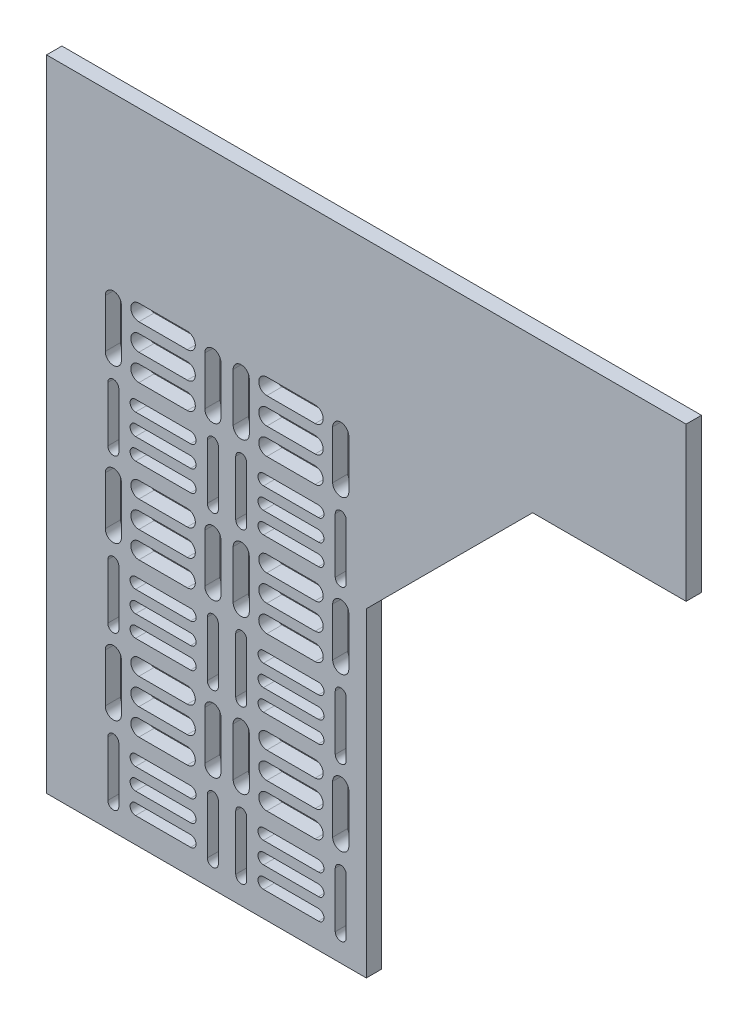
SolidWorks part; units mm, degrees
ref_plane "XY" through (0, 0, 0) normal (0, 0, 1) x (1, 0, 0)
ref_plane "-XZ" through (0, 0, 0) normal (0, 1, 0) x (1, 0, 0)
ref_plane "ZY" through (0, 0, 0) normal (1, 0, 0) x (0, 0, -1)
sketch "Esquisse1" plane through (0, 0, 0) normal (0, 0, 1) x (1, 0, 0)
  line L0 (0, 0) -> (0, 125)
  line L13 (0, 125) -> (125, 125)
  line L19 (125, 125) -> (125, 95)
  line L20 (125, 95) -> (95, 95)
  line L21 (62.5, 62.5) -> (62.5, 0)
  line L22 (62.5, 0) -> (0, 0)
  line L23 (95, 95) -> (62.5, 62.5)
  dimension "D1" = 30
  dimension "D4" = 125
  dimension "D2" = 30
  dimension "D3" = 125
  dimension "D5" = 62.5
  dimension "D6" = 62.5
extrude "Boss.-Extru.1" add sketch "Esquisse1" along normal blind 3 contours L13 L19 L20 L23 L21 L22 L0
sketch "Esquisse2" plane through (0, 0, 3) normal (0, 0, 1) x (1, 0, 0)
  line L0 (43.05, 83.7) -> (52.5, 83.7)
  line L3 (43.05, 90.425) -> (52.5, 90.425) construction
  line L4 (43.05, 92) -> (52.5, 92)
  line L5 (43.05, 88.85) -> (52.5, 88.85)
  line L6 (57.5, 90) -> (57.5, 80.55) construction
  line L7 (59.075, 90) -> (59.075, 80.55)
  line L8 (55.925, 90) -> (55.925, 80.55)
  line L9 (0, 125) -> (125, 125) construction
  line L10 (62.5, 62.5) -> (62.5, 0) construction
  line L11 (43.05, 86.85) -> (52.5, 86.85)
  line L12 (43.05, 78.55) -> (52.5, 78.55)
  line L13 (43.05, 81.7) -> (52.5, 81.7)
  line L18 (42.4, 74.325) -> (53.15, 74.325) construction
  line L28 (47.775, 92) -> (47.775, 88.85) construction
  line L29 (42.4, 75.4) -> (53.15, 75.4)
  line L30 (36.475, 90) -> (36.475, 80.55)
  line L31 (39.625, 90) -> (39.625, 80.55)
  line L32 (42.4, 73.25) -> (53.15, 73.25)
  line L34 (57.5, 64.8) -> (57.5, 75.55) construction
  line L35 (56.425, 75.55) -> (56.425, 64.8)
  line L36 (58.575, 75.55) -> (58.575, 64.8)
  line L37 (47.775, 73.25) -> (47.775, 75.4) construction
  line L38 (42.4, 69.1) -> (53.15, 69.1)
  line L39 (42.4, 71.25) -> (53.15, 71.25)
  line L40 (42.4, 64.95) -> (53.15, 64.95)
  line L41 (42.4, 67.1) -> (53.15, 67.1)
  line L42 (39.125, 75.55) -> (39.125, 64.8)
  line L43 (36.975, 75.55) -> (36.975, 64.8)
  circle A5 centre (43.05, 90.425) radius 1.575 construction
  circle A6 centre (46.2, 90.425) radius 1.575 construction
  circle A7 centre (49.35, 90.425) radius 1.575 construction
  circle A8 centre (52.5, 90.425) radius 1.575 construction
  arc A9 (43.05, 92) -> (43.05, 88.85) centre (43.05, 90.425) ccw
  arc A10 (52.5, 92) -> (52.5, 88.85) centre (52.5, 90.425) cw
  circle A11 centre (57.5, 90) radius 1.575 construction
  circle A12 centre (57.5, 86.85) radius 1.575 construction
  circle A13 centre (57.5, 83.7) radius 1.575 construction
  circle A14 centre (57.5, 80.55) radius 1.575 construction
  arc A15 (59.075, 90) -> (55.925, 90) centre (57.5, 90) ccw
  arc A16 (59.075, 80.55) -> (55.925, 80.55) centre (57.5, 80.55) cw
  arc A17 (52.5, 86.85) -> (52.5, 83.7) centre (52.5, 85.275) cw
  arc A18 (43.05, 86.85) -> (43.05, 83.7) centre (43.05, 85.275) ccw
  arc A19 (52.5, 81.7) -> (52.5, 78.55) centre (52.5, 80.125) cw
  arc A20 (43.05, 81.7) -> (43.05, 78.55) centre (43.05, 80.125) ccw
  arc A41 (36.475, 90) -> (39.625, 90) centre (38.05, 90) cw
  arc A42 (36.475, 80.55) -> (39.625, 80.55) centre (38.05, 80.55) ccw
  circle A45 centre (42.4, 74.325) radius 1.075 construction
  circle A46 centre (44.55, 74.325) radius 1.075 construction
  circle A47 centre (46.7, 74.325) radius 1.075 construction
  circle A48 centre (51, 74.325) radius 1.075 construction
  circle A49 centre (53.15, 74.325) radius 1.075 construction
  circle A50 centre (48.85, 74.325) radius 1.075 construction
  arc A51 (42.4, 75.4) -> (42.4, 73.25) centre (42.4, 74.325) ccw
  arc A52 (53.15, 75.4) -> (53.15, 73.25) centre (53.15, 74.325) cw
  circle A53 centre (57.5, 75.55) radius 1.075 construction
  circle A54 centre (57.5, 64.8) radius 1.075 construction
  circle A55 centre (57.5, 66.95) radius 1.075 construction
  circle A56 centre (57.5, 69.1) radius 1.075 construction
  circle A57 centre (57.5, 71.25) radius 1.075 construction
  circle A58 centre (57.5, 73.4) radius 1.075 construction
  arc A59 (56.425, 75.55) -> (58.575, 75.55) centre (57.5, 75.55) cw
  arc A60 (56.425, 64.8) -> (58.575, 64.8) centre (57.5, 64.8) ccw
  arc A61 (53.15, 71.25) -> (53.15, 69.1) centre (53.15, 70.175) cw
  arc A62 (42.4, 71.25) -> (42.4, 69.1) centre (42.4, 70.175) ccw
  arc A63 (53.15, 67.1) -> (53.15, 64.95) centre (53.15, 66.025) cw
  arc A64 (42.4, 67.1) -> (42.4, 64.95) centre (42.4, 66.025) ccw
  arc A65 (39.125, 64.8) -> (36.975, 64.8) centre (38.05, 64.8) cw
  arc A66 (39.125, 75.55) -> (36.975, 75.55) centre (38.05, 75.55) ccw
  point P11 (47.775, 90.425)
  point P41 (57.5, 85.275)
  point P42 (47.775, 74.325)
  point P62 (57.5, 70.175)
  point P83 (47.775, 90.425)
  point P86 (47.775, 74.325)
  dimension "D1" = 3
  dimension "D2" = 3.15
  dimension "D4" = 35
  dimension "D6" = 2
  dimension "D8" = 2.15
  dimension "D3" = 5
  dimension "D5" = 5
  dimension "D9" = 5
  dimension "D10" = 3
  dimension "D11" = 2
extrude "Enlèv. mat.-Extru.1" cut sketch "Esquisse2" against normal through all both and the other way through all
pattern_linear "Répétition linéaire1" count 2 spacing 25 along (-1, 0, 0) count 3 spacing 30 along (0, -1, 0) of "Enlèv. mat.-Extru.1"
equation "\"D2@Esquisse1\"=\"D1@Esquisse1\""
equation "\"D5@Esquisse1\"=\"D3@Esquisse1\"/2"
equation "\"D6@Esquisse1\"=\"D4@Esquisse1\"/2"
